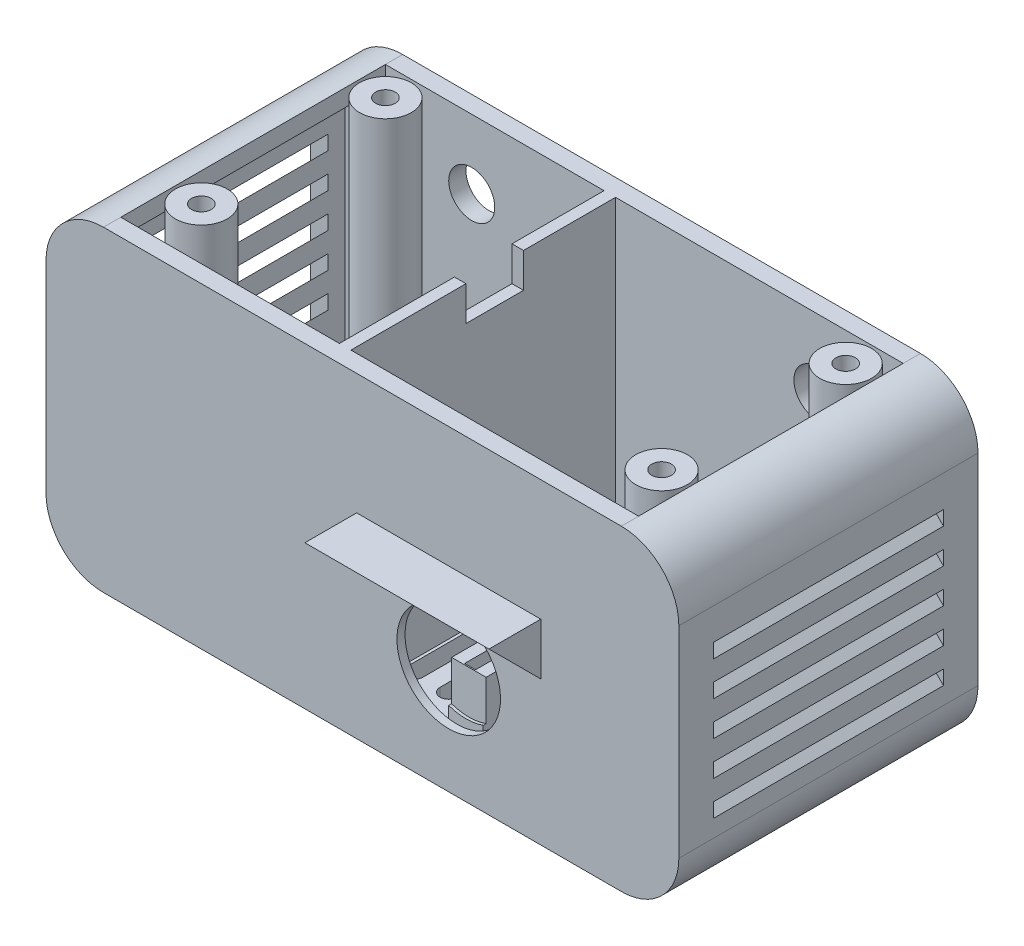
SolidWorks part; units mm, degrees
material "ABS"
ref_plane "Front Plane" through (0, 0, 0) normal (0, 0, 1) x (1, 0, 0)
ref_plane "Top Plane" through (0, 0, 0) normal (0, 1, 0) x (1, 0, 0)
ref_plane "Right Plane" through (0, 0, 0) normal (1, 0, 0) x (0, 0, -1)
sketch "Sketch1" plane through (0, 0, 0) normal (0, 0, 1) x (1, 0, 0)
  line L0 (-45, -55) -> (45, -55)
  line L1 (55, -45) -> (55, -10)
  line L2 (45, 0) -> (-45, 0)
  line L3 (-55, -10) -> (-55, -45)
  arc A0 (45, -55) -> (55, -45) centre (45, -45) ccw
  arc A1 (55, -10) -> (45, 0) centre (45, -10) ccw
  arc A2 (-45, 0) -> (-55, -10) centre (-45, -10) ccw
  arc A3 (-55, -45) -> (-45, -55) centre (-45, -45) ccw
extrude "Boss-Extrude1" add sketch "Sketch1" along normal blind 52
shell "Shell1" thickness 3 removed face at (0, 0, 26)
sketch "Sketch2" plane through (0, 0, 0) normal (0, 1, 0) x (1, 0, 0)
  circle A0 centre (-40, -8) radius 4.5
  circle A1 centre (40, -8) radius 4.5
  circle A2 centre (-40, -40) radius 4.5
  circle A3 centre (40, -40) radius 4.5
extrude "Boss-Extrude2" add sketch "Sketch2" against normal blind 52
sketch "Sketch3" plane through (0, -55, 0) normal (0, -1, 0) x (1, 0, 0)
  circle A0 centre (-40, 8) radius 3.25
  circle A1 centre (40, 8) radius 3.25
  circle A2 centre (-40, 40) radius 3.25
  circle A3 centre (40, 40) radius 3.25
extrude "Cut-Extrude1" cut sketch "Sketch3" against normal blind 49
sketch "Sketch4" plane through (0, -6, 0) normal (0, -1, 0) x (1, 0, 0)
  circle A0 centre (-40, 8) radius 1.7
  circle A1 centre (40, 8) radius 1.7
  circle A2 centre (-40, 40) radius 1.7
  circle A3 centre (40, 40) radius 1.7
extrude "Cut-Extrude2" cut sketch "Sketch4" against normal through all
ref_plane "Plane1" through (0, 0, 26) normal (0, 0, 1) x (1, 0, 0)
sketch "Sketch5" plane through (0, 0, 26) normal (0, 0, 1) x (1, 0, 0)
  line L0 (-51, -14) -> (-51, -11.5)
  line L1 (-51, -11.5) -> (-55.5, -16)
  line L2 (-55.5, -16) -> (-55.5, -18.5)
  line L3 (-55.5, -18.5) -> (-51, -14)
  line L4 (51, -14) -> (51, -11.5)
  line L5 (51, -11.5) -> (55.5, -16)
  line L6 (55.5, -16) -> (55.5, -18.5)
  line L7 (55.5, -18.5) -> (51, -14)
  line L8 (-51, -20) -> (-51, -17.5)
  line L9 (-51, -17.5) -> (-55.5, -22)
  line L10 (-55.5, -22) -> (-55.5, -24.5)
  line L11 (-55.5, -24.5) -> (-51, -20)
  line L12 (51, -20) -> (51, -17.5)
  line L13 (51, -17.5) -> (55.5, -22)
  line L14 (55.5, -22) -> (55.5, -24.5)
  line L15 (55.5, -24.5) -> (51, -20)
  line L16 (-51, -26) -> (-51, -23.5)
  line L17 (-51, -23.5) -> (-55.5, -28)
  line L18 (-55.5, -28) -> (-55.5, -30.5)
  line L19 (-55.5, -30.5) -> (-51, -26)
  line L20 (51, -26) -> (51, -23.5)
  line L21 (51, -23.5) -> (55.5, -28)
  line L22 (55.5, -28) -> (55.5, -30.5)
  line L23 (55.5, -30.5) -> (51, -26)
  line L24 (-51, -32) -> (-51, -29.5)
  line L25 (-51, -29.5) -> (-55.5, -34)
  line L26 (-55.5, -34) -> (-55.5, -36.5)
  line L27 (-55.5, -36.5) -> (-51, -32)
  line L28 (51, -32) -> (51, -29.5)
  line L29 (51, -29.5) -> (55.5, -34)
  line L30 (55.5, -34) -> (55.5, -36.5)
  line L31 (55.5, -36.5) -> (51, -32)
  line L32 (-51, -38) -> (-51, -35.5)
  line L33 (-51, -35.5) -> (-55.5, -40)
  line L34 (-55.5, -40) -> (-55.5, -42.5)
  line L35 (-55.5, -42.5) -> (-51, -38)
  line L36 (51, -38) -> (51, -35.5)
  line L37 (51, -35.5) -> (55.5, -40)
  line L38 (55.5, -40) -> (55.5, -42.5)
  line L39 (55.5, -42.5) -> (51, -38)
extrude "Cut-Extrude3" cut sketch "Sketch5" against normal blind 20 and the other way blind 20
sketch "Sketch6" plane through (0, -55, 0) normal (0, -1, 0) x (1, 0, 0)
  line L0 (-33, 12) -> (-33, 40) construction
  line L1 (-34.5, 12) -> (-34.5, 40)
  line L2 (-31.5, 12) -> (-31.5, 40)
  line L3 (-27, 12) -> (-27, 40) construction
  line L4 (-28.5, 12) -> (-28.5, 40)
  line L5 (-25.5, 12) -> (-25.5, 40)
  line L6 (-21, 12) -> (-21, 40) construction
  line L7 (-22.5, 12) -> (-22.5, 40)
  line L8 (-19.5, 12) -> (-19.5, 40)
  line L9 (-15, 12) -> (-15, 40) construction
  line L10 (-16.5, 12) -> (-16.5, 40)
  line L11 (-13.5, 12) -> (-13.5, 40)
  line L12 (-9, 12) -> (-9, 40) construction
  line L13 (-10.5, 12) -> (-10.5, 40)
  line L14 (-7.5, 12) -> (-7.5, 40)
  line L15 (-3, 12) -> (-3, 40) construction
  line L16 (-4.5, 12) -> (-4.5, 40)
  line L17 (-1.5, 12) -> (-1.5, 40)
  line L18 (3, 12) -> (3, 40) construction
  line L19 (1.5, 12) -> (1.5, 40)
  line L20 (4.5, 12) -> (4.5, 40)
  line L21 (9, 12) -> (9, 40) construction
  line L22 (7.5, 12) -> (7.5, 40)
  line L23 (10.5, 12) -> (10.5, 40)
  line L24 (21, 12) -> (21, 40) construction
  line L25 (19.5, 12) -> (19.5, 40)
  line L26 (22.5, 12) -> (22.5, 40)
  arc A0 (-34.5, 12) -> (-31.5, 12) centre (-33, 12) ccw
  arc A1 (-31.5, 40) -> (-34.5, 40) centre (-33, 40) ccw
  arc A2 (-28.5, 12) -> (-25.5, 12) centre (-27, 12) ccw
  arc A3 (-25.5, 40) -> (-28.5, 40) centre (-27, 40) ccw
  arc A4 (-22.5, 12) -> (-19.5, 12) centre (-21, 12) ccw
  arc A5 (-19.5, 40) -> (-22.5, 40) centre (-21, 40) ccw
  arc A6 (-16.5, 12) -> (-13.5, 12) centre (-15, 12) ccw
  arc A7 (-13.5, 40) -> (-16.5, 40) centre (-15, 40) ccw
  arc A8 (-10.5, 12) -> (-7.5, 12) centre (-9, 12) ccw
  arc A9 (-7.5, 40) -> (-10.5, 40) centre (-9, 40) ccw
  arc A10 (-4.5, 12) -> (-1.5, 12) centre (-3, 12) ccw
  arc A11 (-1.5, 40) -> (-4.5, 40) centre (-3, 40) ccw
  arc A12 (1.5, 12) -> (4.5, 12) centre (3, 12) ccw
  arc A13 (4.5, 40) -> (1.5, 40) centre (3, 40) ccw
  arc A14 (7.5, 12) -> (10.5, 12) centre (9, 12) ccw
  arc A15 (10.5, 40) -> (7.5, 40) centre (9, 40) ccw
  arc A16 (19.5, 12) -> (22.5, 12) centre (21, 12) ccw
  arc A17 (22.5, 40) -> (19.5, 40) centre (21, 40) ccw
  point P2 (-33, 26)
  point P7 (-27, 26)
  point P14 (-21, 26)
  point P21 (-15, 26)
  point P28 (-9, 26)
  point P35 (-3, 26)
  point P42 (3, 26)
  point P49 (9, 26)
  point P56 (21, 26)
  point P63 (0, 0)
extrude "Cut-Extrude4" cut sketch "Sketch6" against normal blind 3.5
sketch "Sketch7" plane through (0, 0, 0) normal (0, 0, -1) x (-1, 0, 0)
  circle A0 centre (30, -12) radius 4
  circle A1 centre (-30, -12) radius 4
extrude "Cut-Extrude5" cut sketch "Sketch7" against normal blind 3.5
sketch "Sketch8" plane through (0, 0, 0) normal (0, 1, 0) x (1, 0, 0)
  line L0 (-30.25, -26) -> (30.25, -26) construction
  line L1 (-7, -49) -> (-5, -49)
  line L2 (-7, -49) -> (-7, -3)
  line L3 (-7, -3) -> (-5, -3)
  line L4 (-5, -49) -> (-5, -3)
  line L5 (-7, -49) -> (-5, -3) construction
  line L6 (-7, -3) -> (-5, -49) construction
  line L7 (45, -3) -> (-45, -3) construction
  point P0 (-6, -26)
extrude "Boss-Extrude3" add sketch "Sketch8" against normal blind 52
sketch "Sketch9" plane through (0, 0, 0) normal (0, 1, 0) x (1, 0, 0)
  line L0 (-4.5, -12) -> (-4.5, -40) construction
  line L1 (-7.5, -29) -> (-4.5, -29)
  line L2 (-7.5, -29) -> (-7.5, -19)
  line L3 (-7.5, -19) -> (-4.5, -19)
  line L4 (-4.5, -29) -> (-4.5, -19)
  line L5 (-7.5, -29) -> (-4.5, -19) construction
  line L6 (-7.5, -19) -> (-4.5, -29) construction
  point P0 (-6, -24)
extrude "Cut-Extrude6" cut sketch "Sketch9" against normal blind 6
sketch "Sketch10" plane through (0, -52, 0) normal (0, 1, 0) x (1, 0, 0)
  line L0 (-30.25, -26) -> (30.25, -26) construction
  line L1 (-47, -36) -> (-41, -36)
  line L2 (-47, -36) -> (-47, -16)
  line L3 (-47, -16) -> (-41, -16)
  line L4 (-41, -36) -> (-41, -16)
  line L5 (-47, -36) -> (-41, -16) construction
  line L6 (-47, -16) -> (-41, -36) construction
  point P0 (-44, -26)
extrude "Boss-Extrude4" add sketch "Sketch10" along normal blind 8
sketch "Sketch11" plane through (0, -44, 0) normal (0, 1, 0) x (1, 0, 0)
  line L0 (-30.25, -26) -> (30.25, -26) construction
  line L1 (-44.95, -34.3) -> (-43.05, -34.3)
  line L2 (-44.95, -34.3) -> (-44.95, -17.7)
  line L3 (-44.95, -17.7) -> (-43.05, -17.7)
  line L4 (-43.05, -34.3) -> (-43.05, -17.7)
  line L5 (-44.95, -34.3) -> (-43.05, -17.7) construction
  line L6 (-44.95, -17.7) -> (-43.05, -34.3) construction
  point P0 (-44, -26)
extrude "Cut-Extrude7" cut sketch "Sketch11" against normal blind 6
sketch "Sketch12" plane through (0, -52, 0) normal (0, 1, 0) x (1, 0, 0)
  line L0 (-30.25, -26) -> (30.25, -26) construction
  line L1 (27, -44.5) -> (33, -44.5)
  line L2 (27, -44.5) -> (27, -7.5)
  line L3 (27, -7.5) -> (33, -7.5)
  line L4 (33, -44.5) -> (33, -7.5)
  line L5 (27, -44.5) -> (33, -7.5) construction
  line L6 (27, -7.5) -> (33, -44.5) construction
  point P0 (30, -26)
extrude "Boss-Extrude5" add sketch "Sketch12" along normal blind 8
sketch "Sketch13" plane through (0, -44, 0) normal (0, 1, 0) x (1, 0, 0)
  line L0 (-30.25, -26) -> (30.25, -26) construction
  line L1 (29.05, -42.8) -> (30.95, -42.8)
  line L2 (29.05, -42.8) -> (29.05, -9.2)
  line L3 (29.05, -9.2) -> (30.95, -9.2)
  line L4 (30.95, -42.8) -> (30.95, -9.2)
  line L5 (29.05, -42.8) -> (30.95, -9.2) construction
  line L6 (29.05, -9.2) -> (30.95, -42.8) construction
  point P0 (30, -26)
extrude "Cut-Extrude8" cut sketch "Sketch13" against normal blind 6
sketch "Sketch14" plane through (0, -52, 0) normal (0, 1, 0) x (1, 0, 0)
  line L1 (12, -50) -> (18, -50)
  line L2 (12, -50) -> (12, -10)
  line L3 (12, -10) -> (18, -10)
  line L4 (18, -50) -> (18, -10)
  line L5 (12, -50) -> (18, -10) construction
  line L6 (12, -10) -> (18, -50) construction
  point P0 (15, -30)
extrude "Boss-Extrude6" add sketch "Sketch14" along normal blind 14
sketch "Sketch15" plane through (0, -38, 0) normal (0, 1, 0) x (1, 0, 0)
  line L1 (14.05, -48.3) -> (15.95, -48.3)
  line L2 (14.05, -48.3) -> (14.05, -11.7)
  line L3 (14.05, -11.7) -> (15.95, -11.7)
  line L4 (15.95, -48.3) -> (15.95, -11.7)
  line L5 (14.05, -48.3) -> (15.95, -11.7) construction
  line L6 (14.05, -11.7) -> (15.95, -48.3) construction
  point P0 (15, -30)
extrude "Cut-Extrude9" cut sketch "Sketch15" against normal blind 12
sketch "Sketch16" plane through (0, 0, 52) normal (0, 0, 1) x (1, 0, 0)
  circle A0 centre (15, -36.5) radius 9
extrude "Cut-Extrude10" cut sketch "Sketch16" against normal blind 3.5
sketch "Sketch17" plane through (0, 0, 49) normal (0, 0, -1) x (-1, 0, 0)
  circle A0 centre (-15, -36.5) radius 12.7
extrude "Cut-Extrude11" cut sketch "Sketch17" against normal blind 1.6
ref_plane "Plane2" through (15, 0, 0) normal (1, 0, 0) x (0, 0, -1)
sketch "Sketch18" plane through (15, 0, 0) normal (1, 0, 0) x (0, 0, -1)
  line L0 (-51, -21) -> (-61, -21)
  line L1 (-61, -21) -> (-51, -31)
  line L2 (-51, -31) -> (-51, -21)
extrude "Boss-Extrude7" add sketch "Sketch18" along normal mid plane 32
